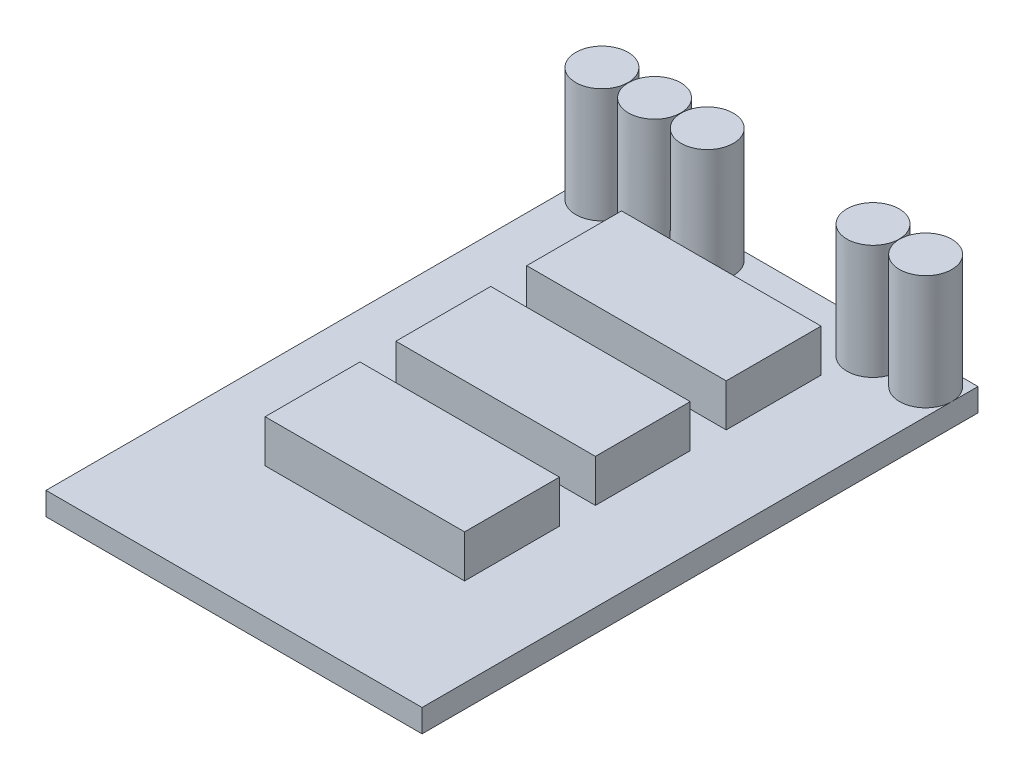
SolidWorks part; units mm, degrees
ref_plane "Спереди" through (0, 0, 0) normal (0, 0, 1) x (1, 0, 0)
ref_plane "Сверху" through (0, 0, 0) normal (0, 1, 0) x (1, 0, 0)
ref_plane "Справа" through (0, 0, 0) normal (1, 0, 0) x (0, 0, -1)
other "Configuration Table"
sketch "Sketch1" plane through (0, 0, 0) normal (0, 1, 0) x (1, 0, 0)
  line L1 (-57.5, 85) -> (57.5, 85)
  line L2 (-57.5, 85) -> (-57.5, -85)
  line L3 (-57.5, -85) -> (57.5, -85)
  line L4 (57.5, 85) -> (57.5, -85)
  line L5 (-57.5, 85) -> (57.5, -85) construction
  line L6 (-57.5, -85) -> (57.5, 85) construction
  point P0 (0, 0)
  dimension "D1" = 115
  dimension "D2" = 170
extrude "Boss-Extrude1" add sketch "Sketch1" along normal blind 7
sketch "Sketch2" plane through (0, 7, 0) normal (0, 1, 0) x (1, 0, 0)
  line L0 (57.5, 85) -> (-57.5, 85) construction
  line L1 (-57.5, 85) -> (-57.5, -85) construction
  line L2 (57.5, -85) -> (57.5, 85) construction
  line L3 (0, 93.731) -> (0, -92.3795) construction
  line L4 (-30.5, 64) -> (30.5, 64)
  line L5 (-30.5, 64) -> (-30.5, 35)
  line L6 (-30.5, 35) -> (30.5, 35)
  line L7 (30.5, 64) -> (30.5, 35)
  line L8 (-30.5, 24) -> (30.5, 24)
  line L9 (-30.5, 24) -> (-30.5, -5)
  line L10 (-30.5, -5) -> (30.5, -5)
  line L11 (30.5, 24) -> (30.5, -5)
  line L12 (-30.5, -16) -> (30.5, -16)
  line L13 (-30.5, -16) -> (-30.5, -45)
  line L14 (-30.5, -45) -> (30.5, -45)
  line L15 (30.5, -16) -> (30.5, -45)
  circle A0 centre (-49.5, 77) radius 8
  circle A1 centre (-33.4, 77) radius 8
  circle A2 centre (-17.3, 77) radius 8
  circle A3 centre (33.4, 77) radius 8
  circle A4 centre (49.5, 77) radius 8
  point P31 (-8.199, 77)
  point P32 (28.1323, 77)
  dimension "D1" = 16
  dimension "D2" = 61
  dimension "D3" = 29
  dimension "D4" = 5
  dimension "D5" = 11
  dimension "D6" = 11
  dimension "D7" = 0.1
  dimension "D8" = 0.1
  dimension "D9" = 0.1
extrude "Boss-Extrude6" add sketch "Sketch2" along normal blind 13 contours L3 L4 L5 L6 | L4 L3 L6 L7 | L8 L3 L10 L11 | L3 L8 L9 L10 | L3 L12 L13 L14 | L12 L3 L14 L15 region at (15.25, 7, -49.5) region at (-15.25, 7, -49.5) region at (15.25, 7, 30.5) region at (-15.25, 7, 30.5) region at (15.25, 7, -9.5) region at (-15.25, 7, -9.5)
extrude "Boss-Extrude9" add sketch "Sketch2<6>" along normal blind 35 contours A0 | A1 | A2 | A3 | A4 region at (-49.5, 7, -77) region at (-33.4, 7, -77) region at (-17.3, 7, -77) region at (33.4, 7, -77) region at (49.5, 7, -77)
sketch "Sketch2<6>" plane through (0, 7, 0) normal (0, 1, 0) x (1, 0, 0) same geometry as "Sketch2"
equation "\"D6@Sketch2\"=\"D5@Sketch2\""
equation "\"D8@Sketch2\"=\"D7@Sketch2\""
equation "\"D9@Sketch2\"=\"D7@Sketch2\""
